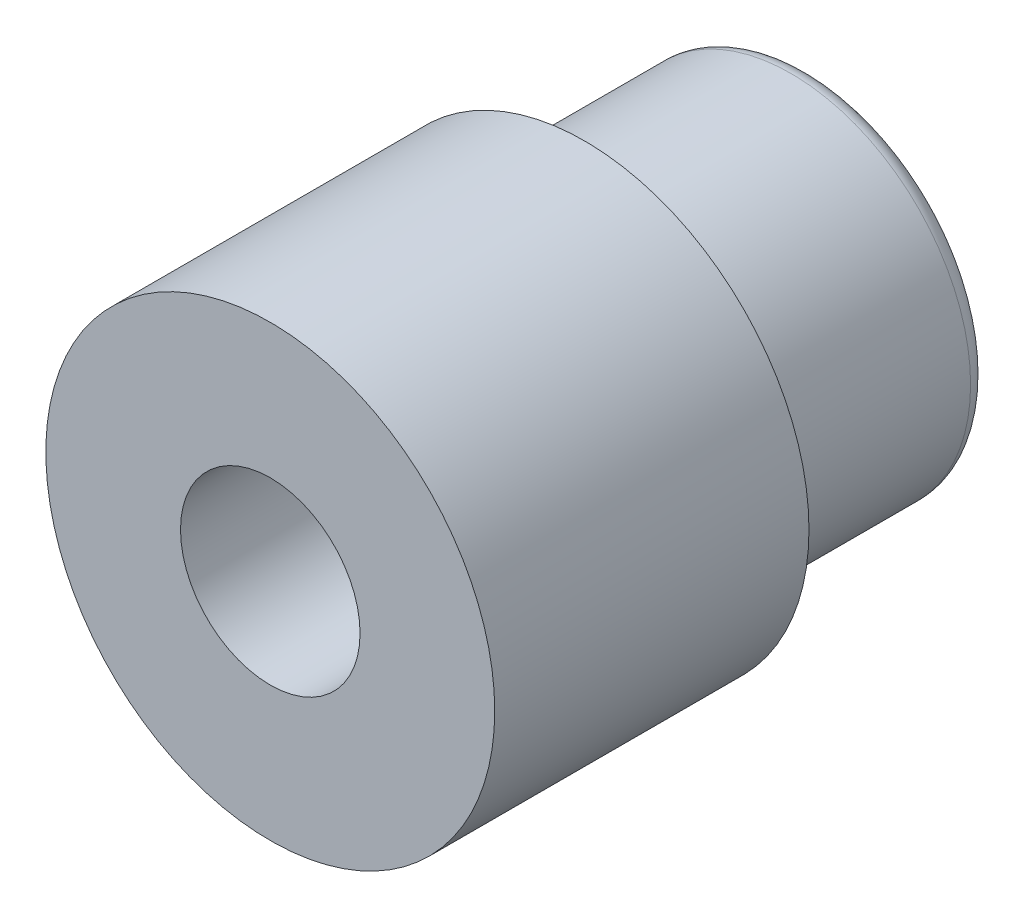
SolidWorks part; units mm, degrees
ref_plane "Vorne" through (0, 0, 0) normal (0, 0, 1) x (1, 0, 0)
ref_plane "Oben" through (0, 0, 0) normal (0, 1, 0) x (1, 0, 0)
ref_plane "Rechts" through (0, 0, 0) normal (1, 0, 0) x (0, 0, -1)
sketch "Skizze1" plane through (0, 0, 0) normal (1, 0, 0) x (0, 0, -1)
  line L0 (0, 0) -> (42.1407, 0) construction
  line L1 (0, 2.5) -> (0, 1)
  line L2 (0, 1) -> (6, 1)
  line L3 (6, 1) -> (6, 2)
  line L4 (6, 2) -> (3.5, 2)
  line L5 (3.5, 2) -> (3.5, 2.5)
  line L6 (3.5, 2.5) -> (0, 2.5)
  dimension "D1" = 2
  dimension "D2" = 4
  dimension "D3" = 5
  dimension "D4" = 6
  dimension "D5" = 3.5
revolve "Rotation1" add sketch "Skizze1" angle 360 about L0
fillet "Verrundung1" radius 0.8 1 edges at (1, 0, -6)
fillet "Verrundung2" radius 0.2 1 edges at (2, 0, -6)
